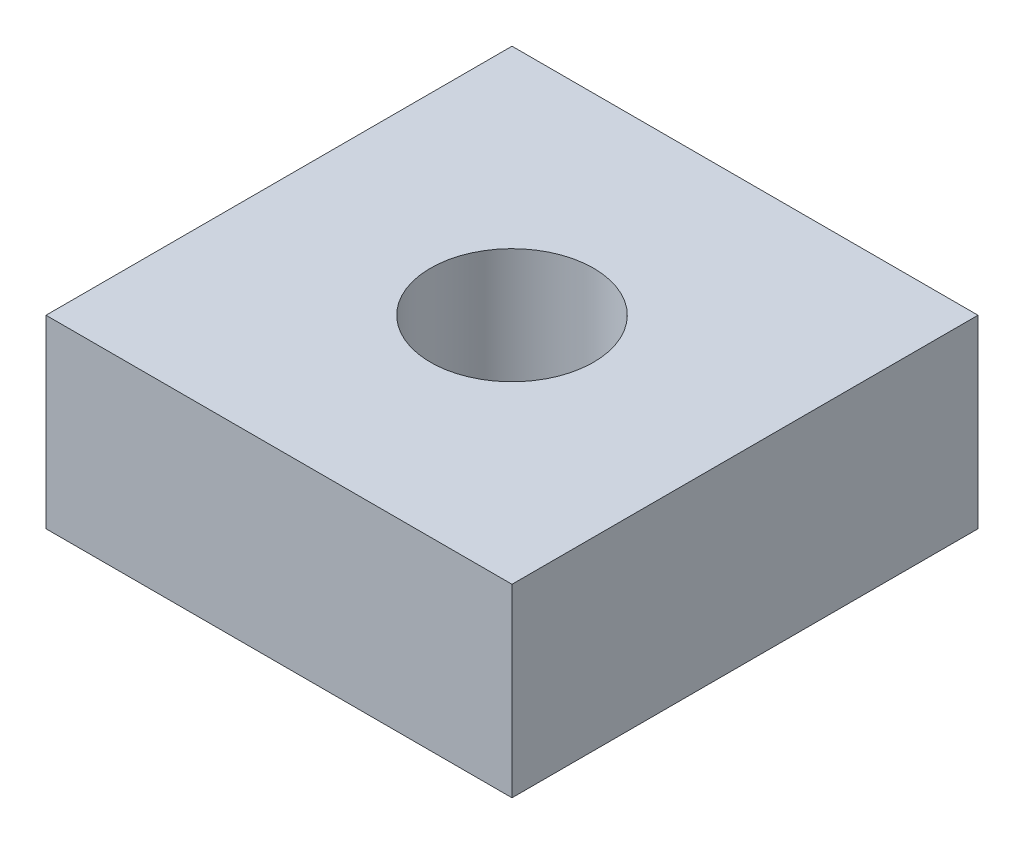
SolidWorks part; units mm, degrees
ref_plane "Front Plane" through (0, 0, 0) normal (0, 0, 1) x (1, 0, 0)
ref_plane "Top Plane" through (0, 0, 0) normal (0, 1, 0) x (1, 0, 0)
ref_plane "Right Plane" through (0, 0, 0) normal (1, 0, 0) x (0, 0, -1)
sketch "Sketch2" plane through (0, 0, 0) normal (0, 1, 0) x (1, 0, 0)
  line L0 (-12, 6) -> (0, 6) construction
  line L1 (0, 0) -> (-12, 0)
  line L2 (0, 0) -> (0, 12)
  line L3 (0, 12) -> (-12, 12)
  line L4 (-12, 0) -> (-12, 12)
  line L5 (-6, 0) -> (-6, 12) construction
  circle A1 centre (-6, 6) radius 2.1
  dimension "D1" = 4.2
extrude "Boss-Extrude1" add sketch "Sketch2" along normal blind 4.7625
